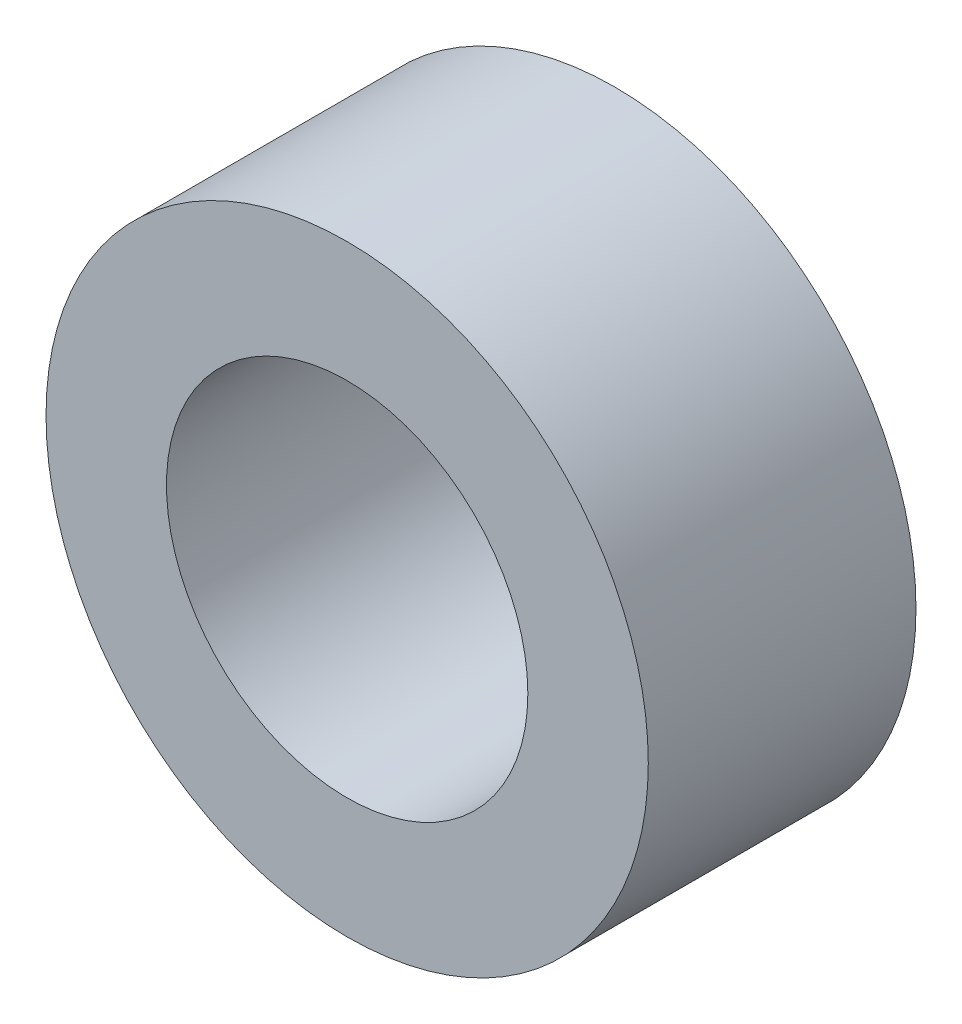
SolidWorks part; units mm, degrees
ref_plane "Front Plane" through (0, 0, 0) normal (0, 0, 1) x (1, 0, 0)
ref_plane "Top Plane" through (0, 0, 0) normal (0, 1, 0) x (1, 0, 0)
ref_plane "Right Plane" through (0, 0, 0) normal (1, 0, 0) x (0, 0, -1)
sketch "Sketch1" plane through (0, 0, 0) normal (0, 0, 1) x (1, 0, 0)
  circle A0 centre (0, 0) radius 2.25
  circle A1 centre (0, 0) radius 1.35
  dimension "OD" = 4.5
  dimension "ID" = 2.7
extrude "Extrude1" add sketch "Sketch1" along normal mid plane 2
sketch "Sketch2" plane through (0, 0, 0) normal (1, 0, 0) x (0, 0, -1)
  line L0 (-1, -1.35) -> (1, -1.35) construction
  line L3 (1, 1.35) -> (-1, 1.35) construction
  line L5 (-1, -1.35) -> (1, -1.35)
  line L6 (1, 1.35) -> (-1, 1.35)
sketch "Sketch4" plane through (0, 0, 1) normal (0, 0, 1) x (1, 0, 0)
  line L0 (0, 0) -> (-0.9546, 0.9546)
  line L1 (0, -1.1) -> (0, 1.1) construction
  circle A0 centre (0, 0) radius 1.35 construction
  dimension "D1" = 45
